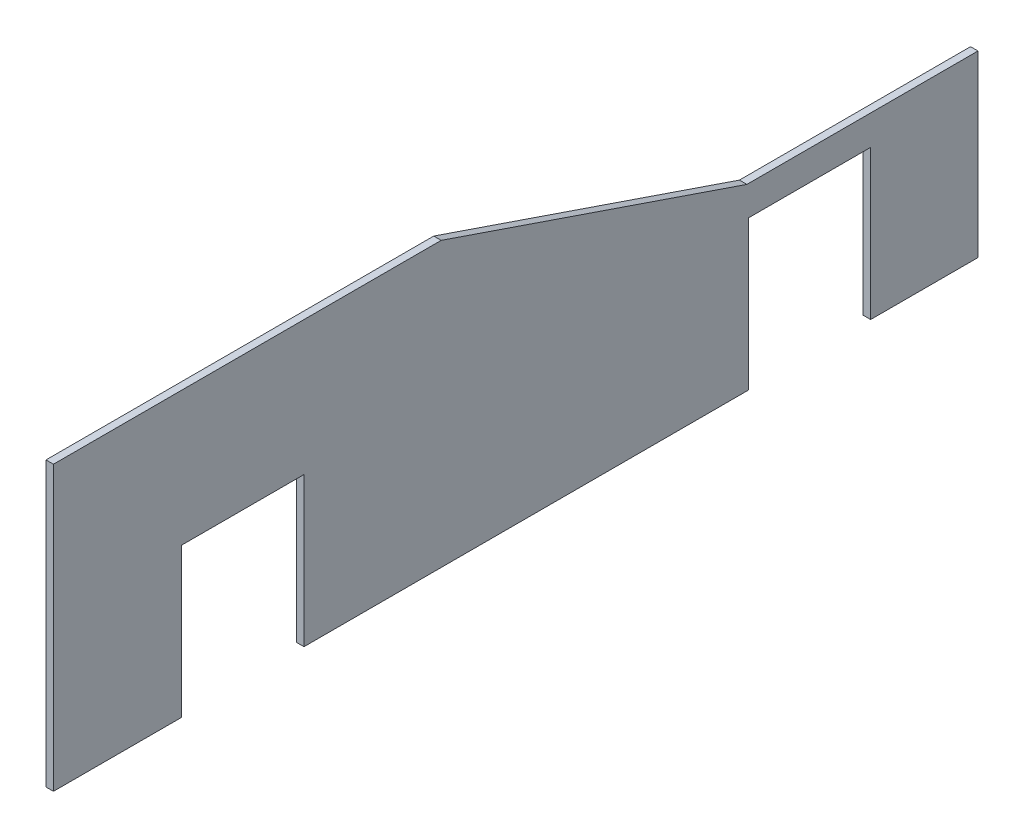
SolidWorks part; units mm, degrees
ref_plane "前视基准面" through (0, 0, 0) normal (0, 0, 1) x (1, 0, 0)
ref_plane "上视基准面" through (0, 0, 0) normal (0, 1, 0) x (1, 0, 0)
ref_plane "右视基准面" through (0, 0, 0) normal (1, 0, 0) x (0, 0, -1)
sketch "Sketch1" plane through (0, 0, 0) normal (1, 0, 0) x (0, 0, -1)
  line L1 (-310, -95) -> (310, -95)
  line L2 (-310, -95) -> (-310, 95)
  line L3 (-310, 95) -> (310, 95)
  line L4 (310, -95) -> (310, 95)
  line L5 (-310, -95) -> (310, 95) construction
  line L6 (-310, 95) -> (310, -95) construction
  point P0 (0, 0)
  dimension "D1" = 620
  dimension "D2" = 190
extrude "Boss-Extrude1" add sketch "Sketch1" along normal blind 5
sketch "Sketch2" plane through (5, 0, 0) normal (1, 0, 0) x (0, 0, -1)
  line L0 (-310, -95) -> (310, -95) construction
  line L1 (-224, -95) -> (-142, -95)
  line L2 (-224, -95) -> (-224, 5)
  line L3 (-224, 5) -> (-142, 5)
  line L4 (-142, -95) -> (-142, 5)
  line L5 (-310, 95) -> (-310, -95) construction
  line L6 (156, -95) -> (238, -95)
  line L7 (156, -95) -> (156, 5)
  line L8 (156, 5) -> (238, 5)
  line L9 (238, -95) -> (238, 5)
  line L10 (310, -95) -> (310, 95) construction
  line L11 (-310, 5) -> (-190, 95)
  line L12 (310, 95) -> (-310, 95) construction
  line L13 (-50, 95) -> (155, 25)
  line L14 (155, 25) -> (310, 25)
  line M9 (310, -95) -> (310, 95)
  line M10 (310, 95) -> (-310, 95)
  line M11 (-310, 95) -> (-310, -95)
  line M12 (-310, -95) -> (310, -95)
  dimension "D1" = 100
  dimension "D2" = 100
  dimension "D3" = 82
  dimension "D4" = 82
  dimension "D5" = 86
  dimension "D6" = 72
  dimension "D7" = 360
  dimension "D8" = 20
  dimension "D9" = 155
  dimension "D10" = 100
  dimension "D11" = 120
extrude "Cut-Extrude1" cut sketch "Sketch2" against normal blind 5 contours L11 M11 M10 | L13 L14 M9 M10 | L4 L3 L2 M12 | L9 L8 L7 M12 region at (5, -45, 183) region at (5, -45, -197) region at (5, 65, 270) region at (5, 64.644, -174.4498)
fillet "Fillet1" [suppressed] radius 2
sketch "Sketch3" plane through (5, 0, 0) normal (1, 0, 0) x (0, 0, -1)
  line L0 (-190, 95) -> (-310, 95)
  line L1 (-310, 5) -> (-310, 95)
  line L2 (-310, 5) -> (-190, 95)
extrude "Boss-Extrude2" add sketch "Sketch3" against normal blind 5
